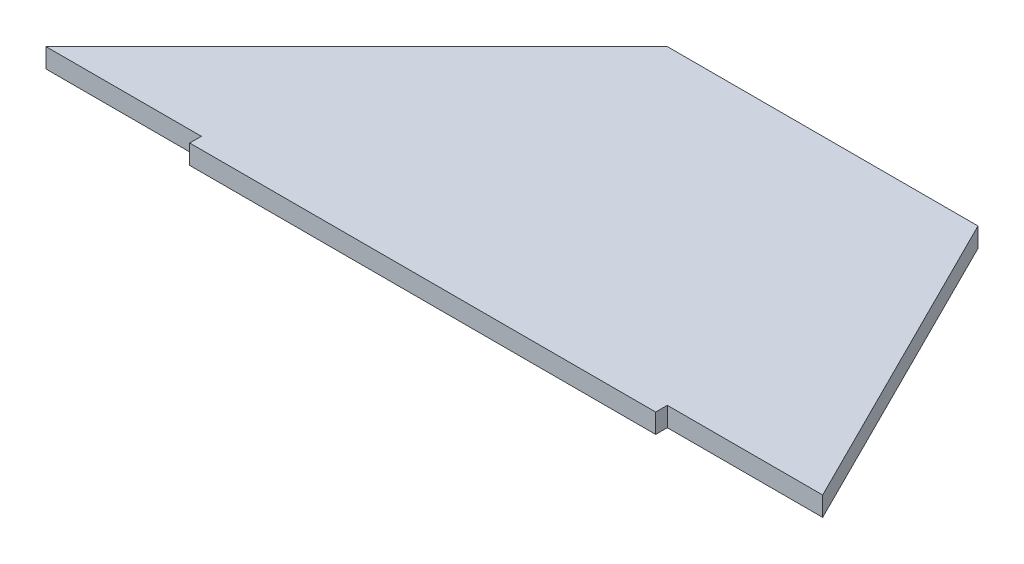
SolidWorks part; units mm, degrees
ref_plane "Front Plane" through (0, 0, 0) normal (0, 0, 1) x (1, 0, 0)
ref_plane "Top Plane" through (0, 0, 0) normal (0, 1, 0) x (1, 0, 0)
ref_plane "Right Plane" through (0, 0, 0) normal (1, 0, 0) x (0, 0, -1)
sketch "Sketch2" plane through (0, 0, 0) normal (0, 1, 0) x (1, 0, 0)
  line L0 (0, 0) -> (152.4, 0)
  line L1 (152.4, 0) -> (152.4, 3.81)
  line L2 (152.4, 3.81) -> (203.2, 3.81)
  line L3 (203.2, 3.81) -> (152.4, 105.41)
  line L4 (152.4, 105.41) -> (50.8, 105.41)
  line L5 (50.8, 105.41) -> (-50.8, 3.81)
  line L6 (-50.8, 3.81) -> (0, 3.81)
  line L7 (0, 3.81) -> (0, 0)
  dimension "D1" = 152.4
  dimension "D2" = 101.6
  dimension "D3" = 50.8
  dimension "D4" = 50.8
  dimension "D5" = 101.6
  dimension "D6" = 3.81
  dimension "D7" = 101.6
extrude "Boss-Extrude1" add sketch "Sketch2" along normal blind 6.35
